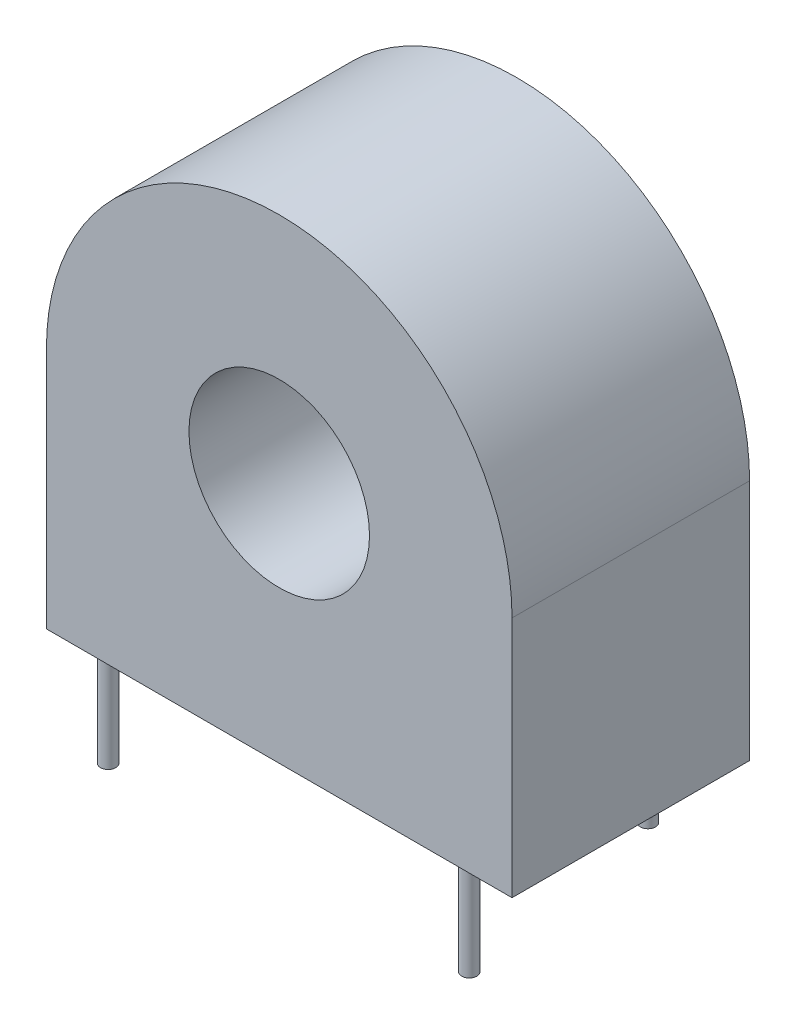
SolidWorks part; units mm, degrees
ref_plane "Front" through (0, 0, 0) normal (0, 0, 1) x (1, 0, 0)
ref_plane "Top" through (0, 0, 0) normal (0, 1, 0) x (1, 0, 0)
ref_plane "Right" through (0, 0, 0) normal (1, 0, 0) x (0, 0, -1)
sketch "Эскиз1" plane through (0, 0, 0) normal (0, 0, 1) x (1, 0, 0)
  line L1 (12.25, -6.375) -> (-12.25, -6.375)
  line L2 (12.25, -6.375) -> (12.25, 6.375)
  line L3 (12.25, 6.375) -> (-12.25, 6.375) construction
  line L4 (-12.25, -6.375) -> (-12.25, 6.375)
  line L5 (12.25, -6.375) -> (-12.25, 6.375) construction
  line L6 (12.25, 6.375) -> (-12.25, -6.375) construction
  arc A0 (12.25, 6.375) -> (-12.25, 6.375) centre (0, 6.375) ccw
  circle A1 centre (0, 6.375) radius 4.75
  point P0 (0, 0)
  dimension "D3" = 9.5
  dimension "D1" = 24.5
  dimension "D2" = 12.75
extrude "Бобышка-Вытянуть1" add sketch "Эскиз1" along normal blind 12.5
sketch "Эскиз2" plane through (0, -6.375, 0) normal (0, -1, 0) x (1, 0, 0)
  line L0 (0, -1000) -> (0, 49000) construction
  line L1 (-12.25, 0) -> (12.25, 0) construction
  line L3 (7.4, 0.5) -> (-7.4, 0.5) construction
  line L4 (9.5, 12) -> (-9.5, 12) construction
  line L5 (-12.25, 12.5) -> (12.25, 12.5) construction
  circle A0 centre (7.4, 0.5) radius 0.4
  circle A1 centre (-7.4, 0.5) radius 0.4
  circle A2 centre (9.5, 12) radius 0.4
  circle A3 centre (-9.5, 12) radius 0.4
  point P7 (0, 0)
  point P9 (0, 0.5)
  point P14 (0, 12)
  dimension "D2" = 0.8
  dimension "D1" = 0.5
  dimension "D3" = 14.8
  dimension "D4" = 19
  dimension "D5" = 0.5
extrude "Бобышка-Вытянуть2" add sketch "Эскиз2" along normal blind 5
ref_axis "Ось1" through (0, 6.375, 12.5) along (0, 0, -1)
